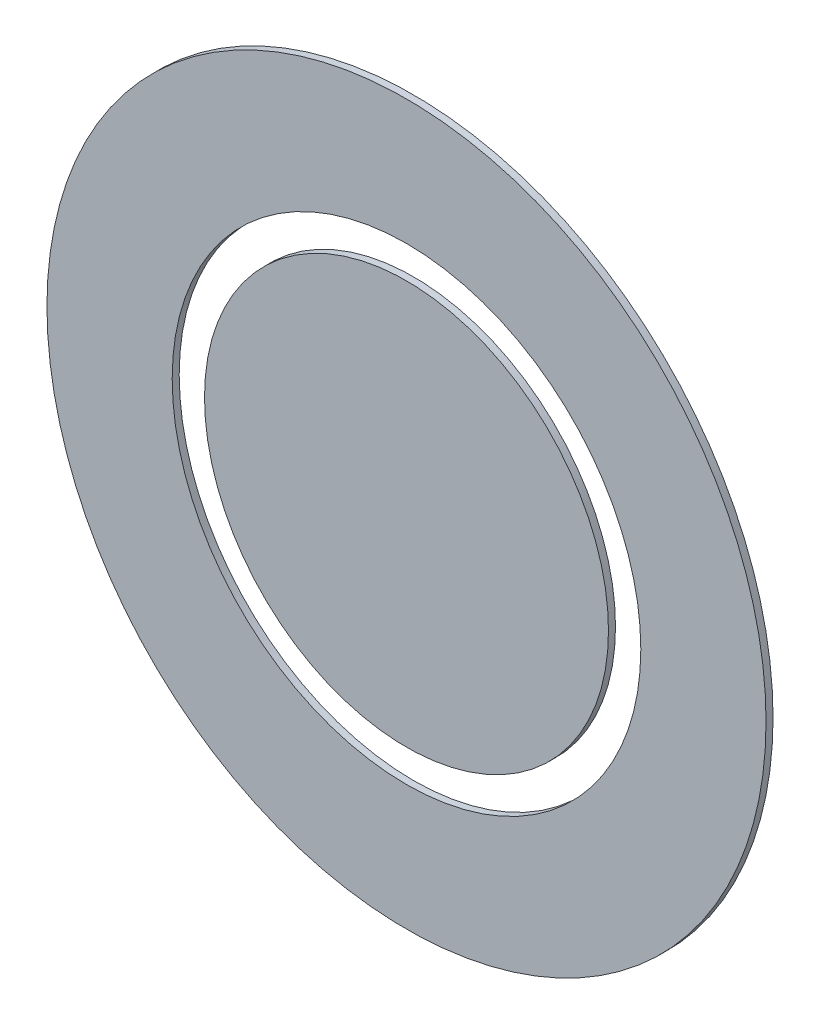
SolidWorks part; units mm, degrees
material "Praseodynium"
ref_plane "Front" through (0, 0, 0) normal (0, 0, 1) x (1, 0, 0)
ref_plane "Top" through (0, 0, 0) normal (0, 1, 0) x (1, 0, 0)
ref_plane "Right" through (0, 0, 0) normal (1, 0, 0) x (0, 0, -1)
sketch "Sketch2" plane through (0, 0, 0) normal (0, 0, 1) x (1, 0, 0)
  circle A0 centre (0, 0) radius 133.5
  circle A1 centre (0, 0) radius 87
  circle A2 centre (0, 0) radius 75
extrude "Boss-Extrude1" add sketch "Sketch2" along normal blind 2.6 contours A2
extrude "Boss-Extrude2" add sketch "Sketch2<3>" along normal blind 2.6 separate body contours A0 A1 region at (-129.724, 0, 0)
sketch "Sketch2<3>" plane through (0, 0, 0) normal (0, 0, 1) x (1, 0, 0) same geometry as "Sketch2"
